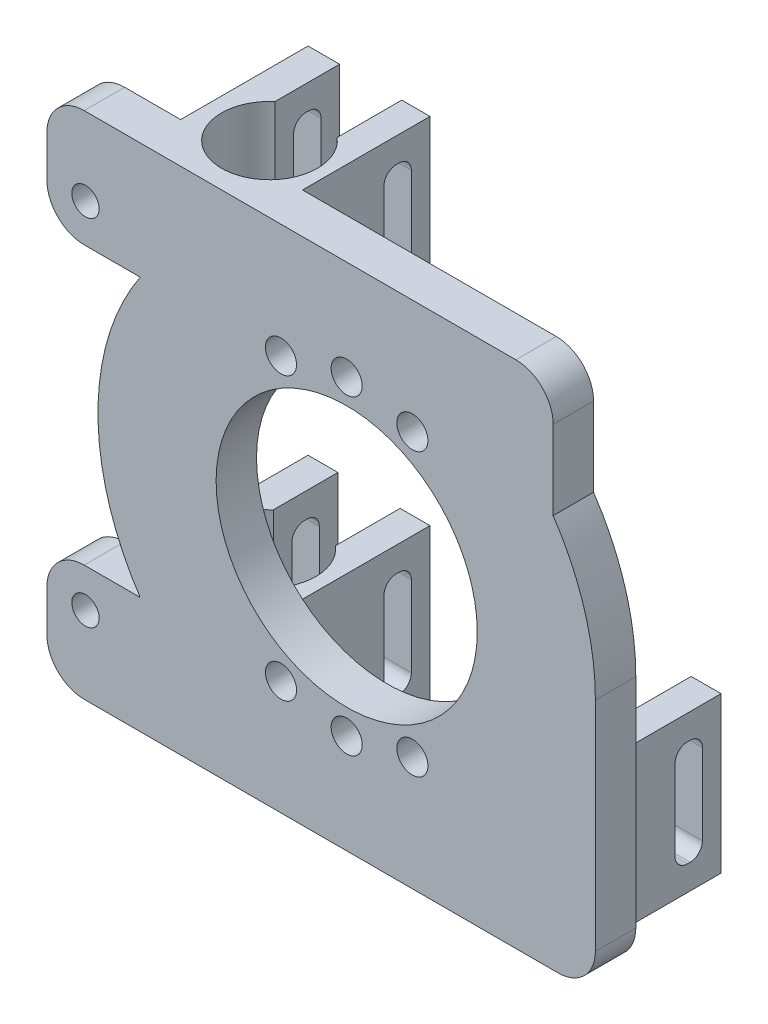
SolidWorks part; units mm, degrees
ref_plane "Front Plane" through (0, 0, 0) normal (0, 0, 1) x (1, 0, 0)
ref_plane "Top Plane" through (0, 0, 0) normal (0, 1, 0) x (1, 0, 0)
ref_plane "Right Plane" through (0, 0, 0) normal (1, 0, 0) x (0, 0, -1)
sketch "Sketch1" plane through (0, 0, 0) normal (0, 0, 1) x (1, 0, 0)
  line L0 (0, 0) -> (0, 27.5) construction
  line L1 (0, 0) -> (11.622, 24.9235) construction
  line L2 (0, 0) -> (-11.622, 24.9235) construction
  line L3 (0, 0) -> (11.622, -24.9235) construction
  line L4 (0, 0) -> (0, -27.5) construction
  line L5 (0, 0) -> (-11.622, -24.9235) construction
  line L6 (0, 0) -> (-60.8338, 0) construction
  line L7 (-40, 0) -> (-40, 22.3) construction
  line L8 (-40, 0) -> (-40, -22.3) construction
  line L9 (-40, -22.3) -> (-33.2071, -22.3) construction
  line L10 (-40, 22.3) -> (-33.2071, 22.3) construction
  line L11 (-33.2071, 22.3) -> (-42.2071, 22.3)
  line L12 (-48.2071, 28.3) -> (-48.2071, 30)
  line L13 (0, 41) -> (-42.2071, 41)
  line L14 (-33.2071, -22.3) -> (-42.2071, -22.3)
  line L15 (-48.2071, -28.3) -> (-48.2071, -30)
  line L17 (-48.2071, 30) -> (-48.2071, 35)
  line L18 (33.2071, 22.3) -> (33.2071, 35)
  line L19 (-13.0397, 22.3) -> (13.0397, 22.3) construction
  line L20 (-48.2071, -30) -> (-48.2071, -34.7)
  line L21 (27.2071, 41) -> (0, 41)
  line L22 (-42.2071, -41) -> (34, -41)
  line L23 (40, 0) -> (40, -35)
  line L24 (-48.2071, -34.7) -> (-48.2071, -35)
  line L25 (0, 41) -> (0, 47.633) construction
  line L26 (19.1186, 41) -> (19.6401, 42.1183) construction
  line L27 (19.1186, -41) -> (24.2233, -51.9471) construction
  line L28 (0, -41) -> (0, -53.438) construction
  line L29 (-19.1186, -41) -> (-24.2529, -52.0105) construction
  circle A0 centre (0, 0) radius 21
  arc A1 (-33.2071, 22.3) -> (-33.2071, -22.3) centre (0, 0) ccw
  circle A2 centre (0, 25) radius 2.5
  circle A3 centre (0, 0) radius 25 construction
  circle A4 centre (10.5655, 22.6577) radius 2.5
  circle A5 centre (-10.5655, 22.6577) radius 2.5
  circle A6 centre (-10.5655, -22.6577) radius 2.5
  circle A7 centre (0, -25) radius 2.5
  circle A8 centre (10.5655, -22.6577) radius 2.5
  circle A9 centre (-42.0071, 28.5) radius 2.2
  circle A10 centre (-42.0071, -28.5) radius 2.2
  arc A11 (-42.2071, -22.3) -> (-48.2071, -28.3) centre (-42.2071, -28.3) ccw
  arc A12 (-42.2071, 22.3) -> (-48.2071, 28.3) centre (-42.2071, 28.3) cw
  arc A13 (-42.2071, -41) -> (-48.2071, -35) centre (-42.2071, -35) cw
  arc A14 (40, -35) -> (34, -41) centre (34, -35) cw
  arc A15 (27.2071, 41) -> (33.2071, 35) centre (27.2071, 35) cw
  arc A16 (-42.2071, 41) -> (-48.2071, 35) centre (-42.2071, 35) ccw
  arc A17 (40, 0) -> (33.2071, 22.3) centre (0, 0) ccw
  point P35 (-42.0071, 28.5)
  point P38 (-42.0071, -28.5)
  point P48 (33.2071, 22.3)
  point P49 (0, 41)
  point P50 (0, 21)
  point P62 (33.2071, 41)
  dimension "D1" = 5
  dimension "D2" = 42
  dimension "D3" = 80
  dimension "D4" = 25
  dimension "D5" = 25
  dimension "D6" = 5
  dimension "D9" = 5
  dimension "D10" = 5
  dimension "D11" = 5
  dimension "D12" = 5
  dimension "D21" = 4.4
  dimension "D24" = 4.4
  dimension "D25" = 6
  dimension "D28" = 6
  dimension "D7" = 25
  dimension "D8" = 25
  dimension "D13" = 22.3
  dimension "D14" = 22.3
  dimension "D16" = 18.7
  dimension "D17" = 15
  dimension "D18" = 15
  dimension "D19" = 6.2
  dimension "D20" = 6.2
  dimension "D22" = 6.2
  dimension "D23" = 6.2
  dimension "D27" = 20
extrude "Base" add sketch "Sketch1" along normal blind 6.5
sketch "Belt_Divets" plane through (0, 0, 0) normal (0, 0, -1) x (-1, 0, 0)
  line L0 (33.8071, 41) -> (33.8071, 22.3)
  line L1 (-27.2071, 41) -> (42.2071, 41) construction
  line L2 (39.8071, 28.5) -> (39.8071, 41)
  line L3 (39.8071, 28.5) -> (39.8071, 22.3)
  line L4 (42.2071, 22.3) -> (33.2071, 22.3) construction
  line L5 (33.8071, 40) -> (39.8071, 40)
  line L6 (33.8071, 39) -> (39.8071, 39)
  line L7 (33.8071, 38) -> (39.8071, 38)
  line L8 (33.8071, 36) -> (39.8071, 36)
  line L9 (33.8071, 37) -> (39.8071, 37)
  line L10 (33.8071, 35) -> (39.8071, 35)
  line L11 (33.8071, 34) -> (39.8071, 34)
  line L12 (33.8071, 33) -> (39.8071, 33)
  line L13 (33.8071, 32) -> (39.8071, 32)
  line L14 (33.8071, 31) -> (39.8071, 31)
  line L15 (33.8071, 30) -> (39.8071, 30)
  line L16 (33.8071, 29) -> (39.8071, 29)
  line L17 (33.8071, 28) -> (39.8071, 28)
  line L18 (33.8071, 27) -> (39.8071, 27)
  line L19 (33.8071, 26) -> (39.8071, 26)
  line L20 (33.8071, 25) -> (39.8071, 25)
  line L21 (33.8071, 24) -> (39.8071, 24)
  line L22 (33.8071, 23) -> (39.8071, 23)
  line L23 (33.8071, 37) -> (33.8071, 36) construction
  line L24 (33.8071, 41) -> (39.8071, 41)
  line L25 (33.8071, 22.3) -> (39.8071, 22.3)
  circle A0 centre (42.0071, 28.5) radius 2.2 construction
  point P7 (39.8071, 28.5)
  point P10 (42.0071, 28.5)
  dimension "D1" = 6
  dimension "D2" = 2.2
  dimension "D3" = 1
  dimension "D4" = 1
  dimension "D5" = 1
  dimension "D6" = 1
  dimension "D8" = 1
  dimension "D7" = 15
extrude "BeltDIvets" cut sketch "Belt_Divets" against normal blind 0.8 contours L0 L22 L3 L21 | L0 L20 L3 L19 | L0 L18 L3 L17 | L0 L16 L2 L15 | L0 L14 L2 L13 | L0 L12 L2 L11 | L0 L10 L2 L8 | L0 L9 L2 L7 | L0 L6 L2 L5 region at (-36.8071, 39.5, 0) region at (-36.8071, 37.5, 0) region at (-36.8071, 35.5, 0) region at (-36.8071, 33.5, 0) region at (-36.8071, 31.5, 0) region at (-36.8071, 29.5, 0) region at (-36.8071, 27.5, 0) region at (-36.8071, 25.5, 0) region at (-36.8071, 23.5, 0)
sketch "Sketch4" plane through (0, 0, 0) normal (0, 0, -1) x (-1, 0, 0)
  line L0 (-27.2071, 41) -> (42.2071, 41) construction
  line L1 (33.2071, 41) -> (13.6015, 41)
  line L2 (33.2071, 41) -> (33.2071, 16)
  line L3 (33.2071, 16) -> (13.6015, 16)
  line L4 (13.6015, 41) -> (13.6015, 16)
  circle A0 centre (0, 0) radius 21 construction
  dimension "D1" = 25
extrude "Bearing1Breakout" add sketch "Sketch4" along normal blind 20.5
sketch "Sketch5" plane through (0, 41, 0) normal (0, 1, 0) x (1, 0, 0)
  line L0 (27.2071, -6.5) -> (-42.2071, -6.5) construction
  line L2 (-28.1357, 20.5) -> (-18.1357, 20.5)
  line L3 (-33.2071, 20.5) -> (-13.6015, 20.5) construction
  line L6 (-18.1357, 14.6039) -> (-18.1357, 10.102)
  line L7 (-28.1357, 14.6039) -> (-28.1357, 10.102)
  line L8 (-28.1357, 14.6039) -> (-28.1357, 20.5)
  line L9 (-18.1357, 14.6039) -> (-18.1357, 20.5)
  arc A0 (-28.1357, 10.102) -> (-18.1357, 10.102) centre (-23.1357, 4.22) ccw
  point P0 (-23.1357, -3.5)
  point P3 (-23.1357, 4.22)
  dimension "D1" = 3
  dimension "D2" = 7.72
extrude "Bearign_Slot_1" cut sketch "Sketch5" against normal blind 25
sketch "Sketch8" plane through (-18.1357, 0, 0) normal (-1, 0, 0) x (0, 0, 1)
  line L0 (-10.102, 16) -> (-20.5, 16) construction
  line L1 (-15.5, 20) -> (-15.102, 20)
  line L2 (-17.5, 22) -> (-17.5, 35)
  line L3 (-15.5, 37) -> (-15.102, 37)
  line L4 (-13.102, 22) -> (-13.102, 35)
  line L5 (-10.102, 41) -> (-20.5, 41) construction
  line L6 (-20.5, 16) -> (-20.5, 41) construction
  line L7 (-10.102, 16) -> (-10.102, 41) construction
  arc A0 (-17.5, 35) -> (-15.5, 37) centre (-15.5, 35) cw
  arc A1 (-15.102, 37) -> (-13.102, 35) centre (-15.102, 35) cw
  arc A2 (-15.102, 20) -> (-13.102, 22) centre (-15.102, 22) ccw
  arc A3 (-15.5, 20) -> (-17.5, 22) centre (-15.5, 22) cw
  dimension "D5" = 2
  dimension "D1" = 4
  dimension "D2" = 4
  dimension "D3" = 3
  dimension "D4" = 3
extrude "ZipTieHoleBearing1" cut sketch "Sketch8" against normal mid plane 31
sketch "Sketch9" plane through (0, 0, 0) normal (0, 0, -1) x (-1, 0, 0)
  line L0 (42.2071, -41) -> (-34, -41) construction
  line L1 (33.2071, -41) -> (13.6015, -41)
  line L2 (33.2071, -41) -> (33.2071, -16)
  line L3 (33.2071, -16) -> (13.6015, -16)
  line L4 (13.6015, -41) -> (13.6015, -16)
  line L5 (13.6015, 41) -> (13.6015, 16) construction
  circle A0 centre (0, 0) radius 21 construction
extrude "Bearin2Breakout" add sketch "Sketch9" along normal blind 20.5
sketch "Sketch10" plane through (0, -41, 0) normal (0, -1, 0) x (1, 0, 0)
  line L0 (-42.2071, 6.5) -> (34, 6.5) construction
  line L1 (-33.2071, -8.8752) -> (-23.4043, -8.8752) construction
  line L2 (-33.2071, -20.5) -> (-33.2071, 0) construction
  line L3 (-13.6015, -20.5) -> (-13.6015, 0) construction
  line L4 (-13.6015, -8.8752) -> (-17.2457, -8.8752) construction
  line L5 (-23.4043, -4.22) -> (-23.4043, 11.0852) construction
  line L7 (-13.6015, -20.5) -> (-33.2071, -20.5) construction
  line L8 (-28.4043, -10.102) -> (-28.4043, -20.5)
  line L9 (-18.4043, -10.102) -> (-18.4043, -20.5)
  line L10 (-28.4043, -20.5) -> (-18.4043, -20.5)
  line L11 (-17.2457, -8.8752) -> (-13.6015, -8.8752) construction
  arc A0 (-18.4043, -10.102) -> (-28.4043, -10.102) centre (-23.4043, -4.22) ccw
  point P0 (-23.4043, 3.5)
  point P1 (-23.4043, -4.22)
  dimension "D1" = 3
  dimension "D2" = 7.72
extrude "Bearing_Slot_2" cut sketch "Sketch10" against normal blind 25
sketch "Sketch13" plane through (0, 0, 0) normal (0, 0, -1) x (-1, 0, 0)
  line L0 (29.8688, -16) -> (16.9398, -16) construction
  line L1 (-13.6015, -16) -> (-33.2115, -16)
  line L2 (-13.6015, -16) -> (-13.6015, -41)
  line L3 (-13.6015, -41) -> (-33.2115, -41)
  line L4 (-33.2115, -16) -> (-33.2115, -41)
  line L5 (13.6015, -41) -> (-34, -41) construction
  arc A0 (13.6015, 16) -> (13.6015, -16) centre (0, 0) ccw construction
  dimension "D1" = 19.61
extrude "Bearing3Breakout" add sketch "Sketch13" along normal blind 20.5
sketch "Sketch14" plane through (0, -41, 0) normal (0, -1, 0) x (1, 0, 0)
  line L1 (33.2115, -20.5) -> (13.6015, -20.5) construction
  line L4 (23.4065, -26.2754) -> (23.4065, -20.5) construction
  line L5 (-42.2071, 6.5) -> (34, 6.5) construction
  line L6 (28.4065, -20.5) -> (28.4065, -10.102)
  line L7 (18.4065, -20.5) -> (18.4065, -10.102)
  line L8 (28.4065, -20.5) -> (18.4065, -20.5)
  arc A0 (28.4065, -10.102) -> (18.4065, -10.102) centre (23.4065, -4.22) ccw
  point P0 (23.4065, 3.5)
  point P1 (23.4065, -4.22)
  point P18 (23.4065, -10.25)
  dimension "D1" = 3
  dimension "D2" = 7.72
  dimension "D3" = 5
  dimension "D4" = 5
extrude "Bearing_Slot_3" cut sketch "Sketch14" against normal blind 25
sketch "Sketch12" plane through (-28.4043, 0, 0) normal (1, 0, 0) x (0, 0, -1)
  line L0 (20.5, -16) -> (20.5, -41) construction
  line L1 (15.5, -20) -> (15.102, -20)
  line L2 (17.5, -22) -> (17.5, -35)
  line L3 (15.5, -37) -> (15.102, -37)
  line L4 (13.102, -22) -> (13.102, -35)
  line L5 (10.102, -16) -> (10.102, -41) construction
  line L6 (10.102, -41) -> (20.5, -41) construction
  line L7 (10.102, -16) -> (20.5, -16) construction
  arc A0 (17.5, -35) -> (15.5, -37) centre (15.5, -35) cw
  arc A1 (15.102, -37) -> (13.102, -35) centre (15.102, -35) cw
  arc A2 (15.102, -20) -> (13.102, -22) centre (15.102, -22) ccw
  arc A3 (15.5, -20) -> (17.5, -22) centre (15.5, -22) cw
  dimension "D5" = 2
  dimension "D1" = 3
  dimension "D2" = 3
  dimension "D3" = 4
  dimension "D4" = 4
extrude "ZipTieHoleBearing2" cut sketch "Sketch12" against normal mid plane 200
